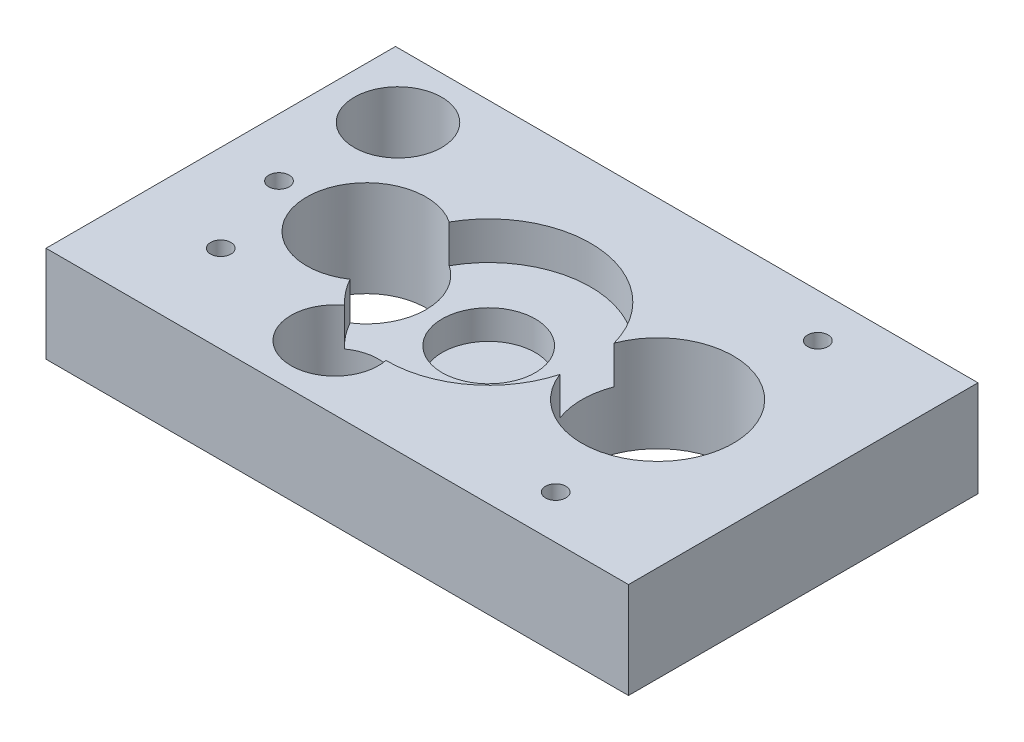
SolidWorks part; units mm, degrees
ref_plane "前视基准面" through (0, 0, 0) normal (0, 0, 1) x (1, 0, 0)
ref_plane "上视基准面" through (0, 0, 0) normal (0, 1, 0) x (1, 0, 0)
ref_plane "右视基准面" through (0, 0, 0) normal (1, 0, 0) x (0, 0, -1)
other "Configuration Table"
sketch "草图1" plane through (0, 0, 0) normal (0, 1, 0) x (1, 0, 0)
  line L1 (0, 0) -> (20, 0)
  line L2 (0, 0) -> (0, -12)
  line L3 (0, -12) -> (20, -12)
  line L4 (20, 0) -> (20, -12)
  circle A0 centre (5, -6) radius 2.05
  circle A4 centre (15, -6) radius 2.6
  circle A5 centre (9.2, -6) radius 1.6
  dimension "D2" = 4.1
  dimension "D3" = 3.2
  dimension "D4" = 20
  dimension "D5" = 5.2
  dimension "D9" = 5
  dimension "D10" = 6
  dimension "D11" = 12
extrude "凸台-拉伸1" add sketch "草图1" along normal blind 2 contours L1 L4 L3 L2 | A0 | A4
extrude "切除-拉伸6" cut sketch "草图1<3>" against normal blind 1 from surface contours A5 starting at face at (5, 2, 8.05)
sketch "草图1<3>" plane through (0, 0, 0) normal (0, 1, 0) x (1, 0, 0) same geometry as "草图1"
sketch "草图3" plane through (0, 2, 0) normal (0, 1, 0) x (1, 0, 0)
  line L1 (0, 0) -> (20, 0)
  line L2 (0, 0) -> (0, -12)
  line L3 (0, -12) -> (20, -12)
  line L4 (20, 0) -> (20, -12)
  circle A0 centre (5, -6) radius 2.05
  circle A1 centre (5, -6) radius 2.05 construction
  circle A3 centre (9.2, -6) radius 1.6 construction
  circle A4 centre (9.2, -6) radius 3.5
  circle M4 centre (15, -6) radius 2.6
  line M5 (0, 0) -> (0, -12)
  line M6 (0, -12) -> (20, -12)
  line M7 (20, -12) -> (20, 0)
  line M8 (20, 0) -> (0, 0)
  dimension "D1" = 7
extrude "凸台-拉伸3" add sketch "草图3" along normal blind 1.3 contours A4 A0 M4 M8 M5 M6 M7 region at (10, 2, 0.2332)
sketch "草图5" plane through (0, 0, 0) normal (0, 1, 0) x (1, 0, 0)
  circle A0 centre (2.3, -2.2142) radius 0.9
  circle A1 centre (7.7, -9.7858) radius 0.9
  circle A4 centre (2.3, -2.2142) radius 1.5
  circle A5 centre (7.7, -9.7858) radius 1.5
  dimension "D1" = 1.8
  dimension "D2" = 3
extrude "切除-拉伸1" cut sketch "草图5" against normal through all from surface contours A1 | A0 starting at face at (9.9453, 3.3, 6)
extrude "切除-拉伸3" cut sketch "草图5<10>" against normal offset from surface (2.8 mm away) 0.5 from surface contours A5 | A4 up to face at (7.7, 0, 10.6858) starting at face at (9.2059, 3.3, 7.0886)
sketch "草图5<10>" plane through (0, 0, 0) normal (0, 1, 0) x (1, 0, 0) same geometry as "草图5"
sketch "草图7" plane through (0, 3.3, 0) normal (0, 1, 0) x (1, 0, 0)
  line L0 (0, -12) -> (20, -12) construction
  line L1 (0, 0) -> (0, -12) construction
  line L2 (20, 0) -> (0, 0) construction
  line L3 (20, -12) -> (20, 0) construction
  line L4 (20, 0) -> (0, 0) construction
  circle A0 centre (2, -6) radius 0.35
  circle A1 centre (3, -9) radius 0.35
  circle A2 centre (16, -1.5) radius 0.35
  circle A3 centre (16, -10.5) radius 0.35
  dimension "D1" = 0.7
  dimension "D2" = 3
  dimension "D3" = 3
  dimension "D4" = 1.5
  dimension "D5" = 1.5
  dimension "D6" = 4
  dimension "D7" = 4
  dimension "D8" = 2
  dimension "D9" = 6
extrude "切除-拉伸4" cut sketch "草图7" against normal blind 2
